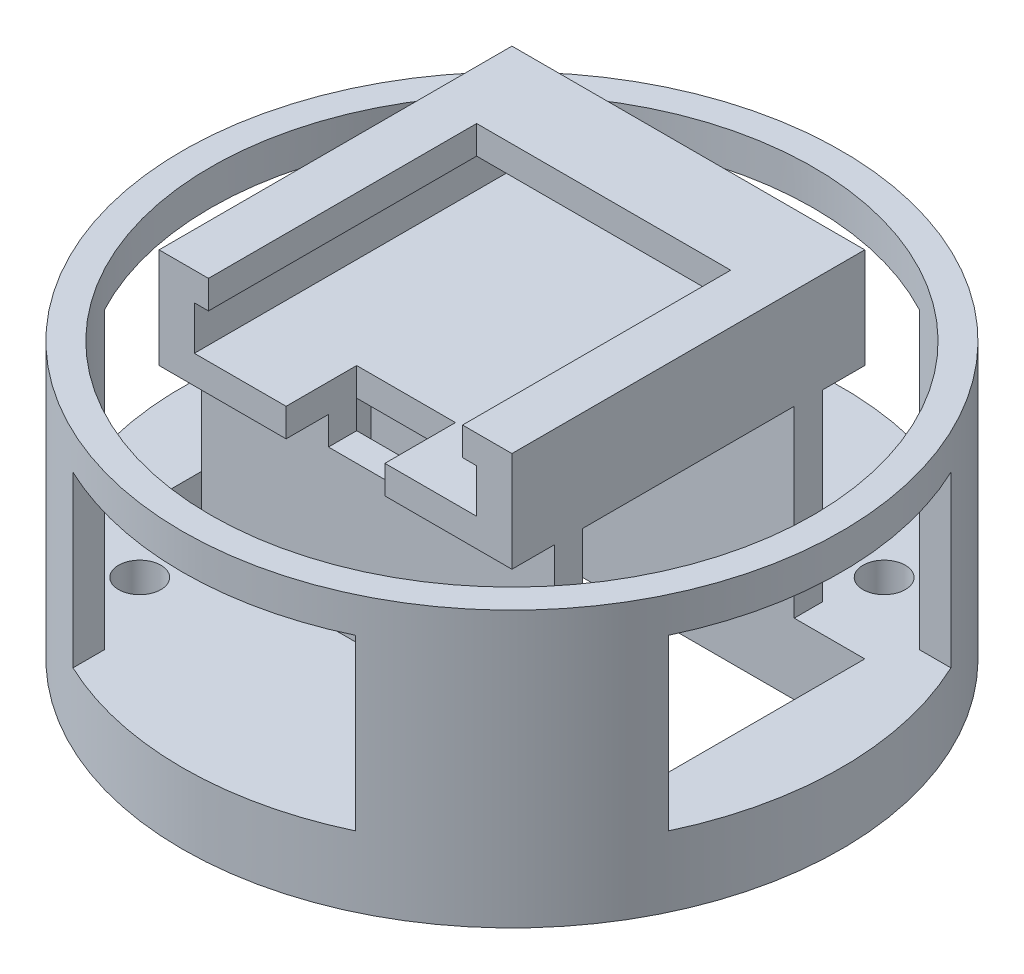
SolidWorks part; units mm, degrees
ref_plane "Plan de face" through (0, 0, 0) normal (0, 0, 1) x (1, 0, 0)
ref_plane "Plan de dessus" through (0, 0, 0) normal (0, 1, 0) x (1, 0, 0)
ref_plane "Plan de droite" through (0, 0, 0) normal (1, 0, 0) x (0, 0, -1)
sketch "Esquisse1" plane through (0, 0, 0) normal (0, 1, 0) x (1, 0, 0)
  circle A0 centre (0, 0) radius 23.35
  dimension "D1" = 46.7
extrude "Boss.-Extru.1" add sketch "Esquisse1" along normal blind 5
sketch "Esquisse9" plane through (0, 5, 0) normal (0, 1, 0) x (1, 0, 0)
  line L0 (-18.1854, 11.1854) -> (-13.1854, 11.1854) construction
  line L17 (-11.1854, 13.1854) -> (-11.1854, 18.1854) construction
  line L19 (-12.5, 7.5) -> (-12.5, 9.5)
  line L20 (-17.5, 7.5) -> (17.5, 7.5)
  line L21 (-17.5, 7.5) -> (-17.5, -7.5)
  line L22 (-17.5, -7.5) -> (17.5, -7.5)
  line L23 (17.5, 7.5) -> (17.5, -7.5)
  line L24 (-12.5, 9.5) -> (12.5, 9.5)
  line L25 (12.5, 9.5) -> (12.5, 7.5)
  line L26 (-17.5, 0) -> (17.5, 0) construction
  line L27 (12.5, -9.5) -> (12.5, -7.5)
  line L28 (-12.5, -9.5) -> (12.5, -9.5)
  line L29 (-12.5, -7.5) -> (-12.5, -9.5)
  circle A1 centre (0, 0) radius 21.35 construction
  arc A2 (-11.1854, 13.1854) -> (-13.1854, 11.1854) centre (-13.1854, 13.1854) cw construction
  circle A3 centre (-13.1854, 13.1854) radius 1.5
  circle A4 centre (13.1854, 13.1854) radius 1.5
  circle A5 centre (13.1854, -13.1854) radius 1.5
  circle A6 centre (-13.1854, -13.1854) radius 1.5
  circle A7 centre (0, 15.3036) radius 2
  circle A8 centre (-7, 15.3036) radius 2.25
  point P11 (-12.5, 8.5)
  point P21 (-11.1854, 11.1854)
  dimension "D10" = 42.7
  dimension "D13" = 2
  dimension "D14" = 3
  dimension "D15" = 4
  dimension "D9" = 4.5
  dimension "D16" = 4
  dimension "D17" = 7
  dimension "D2" = 15
  dimension "D3" = 7.5
  dimension "D4" = 2
  dimension "D5" = 25
  dimension "D6" = 12.5
  dimension "D7" = 35
  dimension "D8" = 17.5
  dimension "D11" = 7
  dimension "D12" = 7
extrude "Enlèv. mat.-Extru.2" cut sketch "Esquisse9" against normal blind 5 contours A3 | A4 | A5 | A6 | A8 | A7 | L21 L20 L23 L22 region at (-13.1854, 5, -13.1854) region at (13.1854, 5, -13.1854) region at (13.1854, 5, 13.1854) region at (-13.1854, 5, 13.1854) region at (0, 5, -15.3036) region at (-7, 5, -15.3036)
extrude "Boss.-Extru.2" add sketch "Esquisse9<3>" along normal blind 15 contours L25 L24 L19 L20 | L22 L29 L28 L27 region at (0, 5, -8.5) region at (0, 5, 8.5)
sketch "Esquisse9<3>" plane through (0, 5, 0) normal (0, 1, 0) x (1, 0, 0) same geometry as "Esquisse9"
sketch "Esquisse11" plane through (0, 20, 0) normal (0, 1, 0) x (1, 0, 0)
  line L0 (-12.5, 9.5) -> (-12.5, -9.5)
  line L5 (-12.5, -9.5) -> (-12.5, -12.5)
  line L6 (-12.5, -12.5) -> (12.5, -12.5)
  line L7 (12.5, -12.5) -> (12.5, 12.5)
  line L8 (12.5, 12.5) -> (-12.5, 12.5)
  line L9 (-12.5, 12.5) -> (-12.5, 9.5)
  dimension "D1" = 25
  dimension "D2" = 12.5
extrude "Boss.-Extru.3" add sketch "Esquisse11" against normal blind 2 contours L0 L5 L6 L7 L8 L9
sketch "Esquisse12" plane through (0, 20, 0) normal (0, 1, 0) x (1, 0, 0)
  line L0 (-10, -12.5) -> (-10, 10)
  line L1 (-12.5, -12.5) -> (12.5, -12.5) construction
  line L2 (-10, 10) -> (10, 10)
  line L3 (10, 10) -> (10, -12.5)
  line L4 (-12.5, -12.5) -> (-12.5, 12.5) construction
  line L10 (12.5, -12.5) -> (12.5, 12.5)
  line L11 (12.5, 12.5) -> (-12.5, 12.5)
  line L12 (-12.5, 12.5) -> (-12.5, -12.5)
  line L13 (-12.5, -12.5) -> (12.5, -12.5)
  line L17 (-10, -12.5) -> (10, -12.5)
  line M4 (12.5, -12.5) -> (12.5, 12.5)
  line M5 (12.5, 12.5) -> (-12.5, 12.5)
  line M6 (-12.5, 12.5) -> (-12.5, -12.5)
  line M7 (-12.5, -12.5) -> (12.5, -12.5)
  dimension "D1" = 2.5
  dimension "D2" = 20
  dimension "D3" = 22.5
  dimension "D4" = 0
extrude "Boss.-Extru.4" add sketch "Esquisse12" along normal blind 3.1 contours L2 L3 L0 M7 M4 M5 M6 region at (-11.25, 20, 12.1464)
sketch "Esquisse13" plane through (0, 23.1, 0) normal (0, 1, 0) x (1, 0, 0)
  line L0 (-10, -12.5) -> (10, -12.5) construction
  line L2 (-9, -12.5) -> (-9, 6.5)
  line L3 (-9, 6.5) -> (9, 6.5)
  line L4 (9, -12.5) -> (9, 6.5)
  line L5 (-9, -12.5) -> (-12.5, -12.5)
  line L6 (-12.5, -12.5) -> (-12.5, 12.5)
  line L7 (-12.5, 12.5) -> (12.5, 12.5)
  line L8 (12.5, 12.5) -> (12.5, -12.5)
  line L9 (12.5, -12.5) -> (9, -12.5)
  dimension "D1" = 18
  dimension "D2" = 9
extrude "Boss.-Extru.5" add sketch "Esquisse13" along normal blind 2 contours L2 L3 L4 L9 L8 L7 L6 L5
sketch "Esquisse14" plane through (0, 5, 0) normal (0, 1, 0) x (1, 0, 0)
  line L0 (-21.1003, 10) -> (-18.8633, 10)
  line L1 (-21.1003, -10) -> (-18.8633, -10)
  line L2 (10, 21.1003) -> (10, 18.8633)
  line L3 (-10, 21.1003) -> (-10, 18.8633)
  line L4 (21.1003, -10) -> (18.8633, -10)
  line L5 (21.1003, 10) -> (18.8633, 10)
  line L6 (-10, -21.1003) -> (-10, -18.8633)
  line L7 (10, -21.1003) -> (10, -18.8633)
  circle A0 centre (0, 0) radius 23.35
  circle A1 centre (0, 0) radius 21.35
  point P23 (0, 0)
  circle M9 centre (0, 0) radius 23.35
  dimension "D1" = 42.7
  dimension "D3" = 46.7
  dimension "D2" = 10
  dimension "D4" = 10
extrude "Boss.-Extru.6" add sketch "Esquisse14" along normal blind 12 contours A1 L7 L4 M9 | A1 L1 L6 M9 | A1 L3 L0 M9 | A1 L5 L2 M9 region at (-15.5577, 5, -15.5577) region at (-15.5577, 5, 15.5577) region at (15.5577, 5, -15.5577) region at (15.5577, 5, 15.5577)
sketch "Esquisse15" plane through (0, 17, 0) normal (0, 1, 0) x (1, 0, 0)
  circle A0 centre (0, 0) radius 23.35
  circle A1 centre (0, 0) radius 21.35
extrude "Boss.-Extru.7" add sketch "Esquisse15" along normal blind 2.5
sketch "Esquisse16" plane through (0, 20, 0) normal (0, 1, 0) x (1, 0, 0)
  line L0 (-10, -12.5) -> (10, -12.5) construction
  line L1 (-3.5, -12.5) -> (-3.5, -7.5)
  line L2 (-3.5, -7.5) -> (3.5, -7.5)
  line L3 (3.5, -7.5) -> (3.5, -12.5)
  line M5 (-10, -12.5) -> (10, -12.5)
  dimension "D1" = 7
  dimension "D2" = 5
  dimension "D3" = 3.5
extrude "Enlèv. mat.-Extru.4" cut sketch "Esquisse16" against normal blind 4 and the other way through all contours L3 L2 L1 M5 region at (0, 20, 10)
